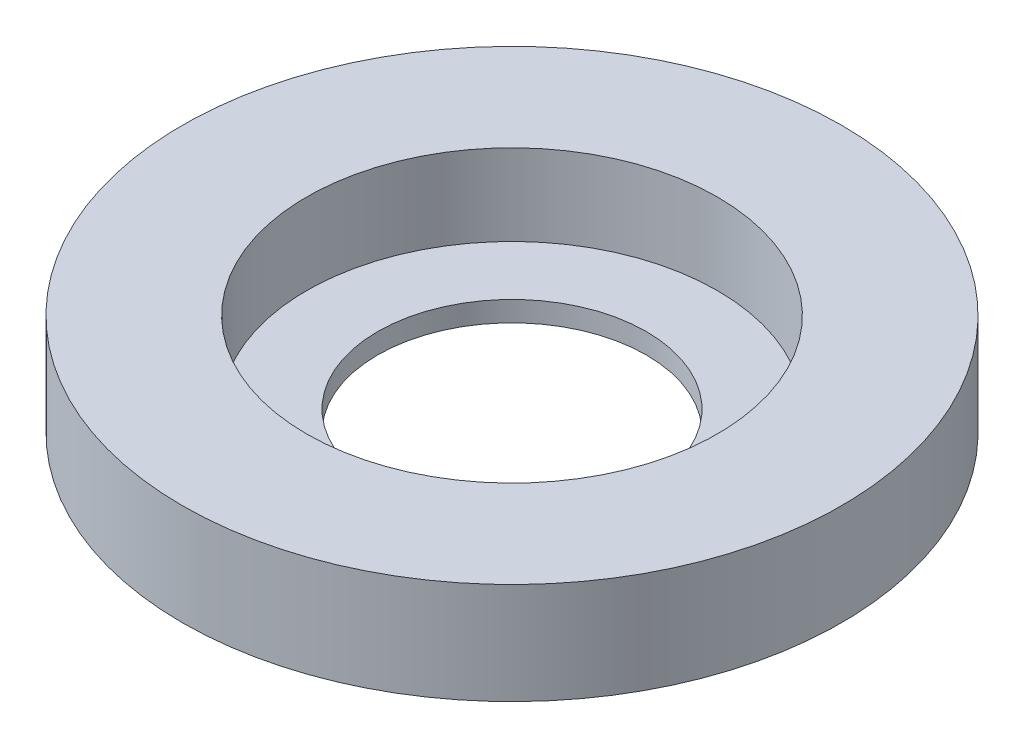
SolidWorks part; units mm, degrees
ref_plane "Front Plane" through (0, 0, 0) normal (0, 0, 1) x (1, 0, 0)
ref_plane "Top Plane" through (0, 0, 0) normal (0, 1, 0) x (1, 0, 0)
ref_plane "Right Plane" through (0, 0, 0) normal (1, 0, 0) x (0, 0, -1)
sketch "Sketch1" plane through (0, 0, 0) normal (0, 0, 1) x (1, 0, 0)
  line L0 (0, 0) -> (0, 7.6914) construction
  line L1 (5.3, 0) -> (13, 0)
  line L2 (13, 0) -> (13, 4)
  line L3 (13, 4) -> (8.1, 4)
  line L4 (8.1, 4) -> (8.1, 0.8)
  line L5 (8.1, 0.8) -> (5.3, 0.8)
  line L6 (5.3, 0.8) -> (5.3, 0)
  point P5 (7.8153, 4)
  dimension "D1" = 0.8
  dimension "D2" = 26
  dimension "D3" = 4
  dimension "D4" = 10.6
  dimension "D5" = 16.2
revolve "Revolve1" add sketch "Sketch1" angle 360 about L0
